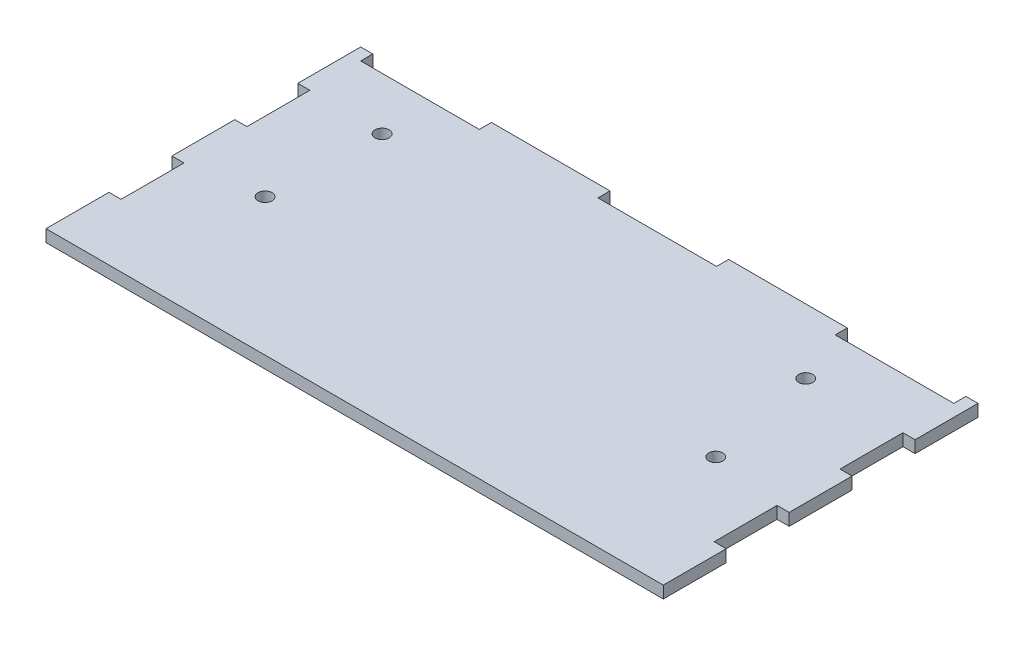
SolidWorks part; units mm, degrees
ref_plane "Front Plane" through (0, 0, 0) normal (0, 0, 1) x (1, 0, 0)
ref_plane "Top Plane" through (0, 0, 0) normal (0, 1, 0) x (1, 0, 0)
ref_plane "Right Plane" through (0, 0, 0) normal (1, 0, 0) x (0, 0, -1)
sketch "Sketch1" plane through (0, 0, 0) normal (0, 1, 0) x (1, 0, 0)
  line L6 (-73.5, 33) -> (-44.1, 33)
  line L12 (-73.5, 20.4) -> (-73.5, 4.8)
  line L14 (-76.5, 36) -> (-73.5, 36)
  line L16 (-76.5, 36) -> (-76.5, 20.4)
  line L20 (-76.5, 4.8) -> (-76.5, -10.8)
  line L23 (-76.5, -26.4) -> (-76.5, -42)
  line L24 (-76.5, -26.4) -> (-73.5, -26.4)
  line L25 (-76.5, -10.8) -> (-73.5, -10.8)
  line L26 (-76.5, 4.8) -> (-73.5, 4.8)
  line L27 (-76.5, 20.4) -> (-73.5, 20.4)
  line L29 (-73.5, 33) -> (-73.5, 36)
  line L30 (-73.5, -10.8) -> (-73.5, -26.4)
  line L31 (14.7, 36) -> (44.1, 36)
  line L32 (76.5, -26.4) -> (76.5, -42)
  line L33 (76.5, -26.4) -> (73.5, -26.4)
  line L34 (73.5, -10.8) -> (73.5, -26.4)
  line L35 (76.5, -10.8) -> (73.5, -10.8)
  line L36 (76.5, 4.8) -> (76.5, -10.8)
  line L37 (76.5, 4.8) -> (73.5, 4.8)
  line L38 (73.5, 20.4) -> (73.5, 4.8)
  line L39 (76.5, 20.4) -> (73.5, 20.4)
  line L40 (76.5, 36) -> (76.5, 20.4)
  line L41 (73.5, 33) -> (73.5, 36)
  line L43 (-14.7, 33) -> (14.7, 33)
  line L44 (73.5, 36) -> (76.5, 36)
  line L45 (44.1, 33) -> (73.5, 33)
  line L46 (-44.1, 33) -> (-44.1, 36)
  line L47 (-14.7, 33) -> (-14.7, 36)
  line L48 (14.7, 33) -> (14.7, 36)
  line L49 (44.1, 33) -> (44.1, 36)
  line L50 (-44.1, 36) -> (-14.7, 36)
  line L62 (-76.5, -42) -> (76.5, -42)
  circle A0 centre (-56.2, -8) radius 1.75
  circle A1 centre (-55.2, 20) radius 1.75
  circle A2 centre (49.8, 20) radius 1.75
  circle A3 centre (55.5, -8) radius 1.75
  point P0 (0, 0)
  point P4 (0, 0)
extrude "Boss-Extrude1" add sketch "Sketch1" along normal blind 3
